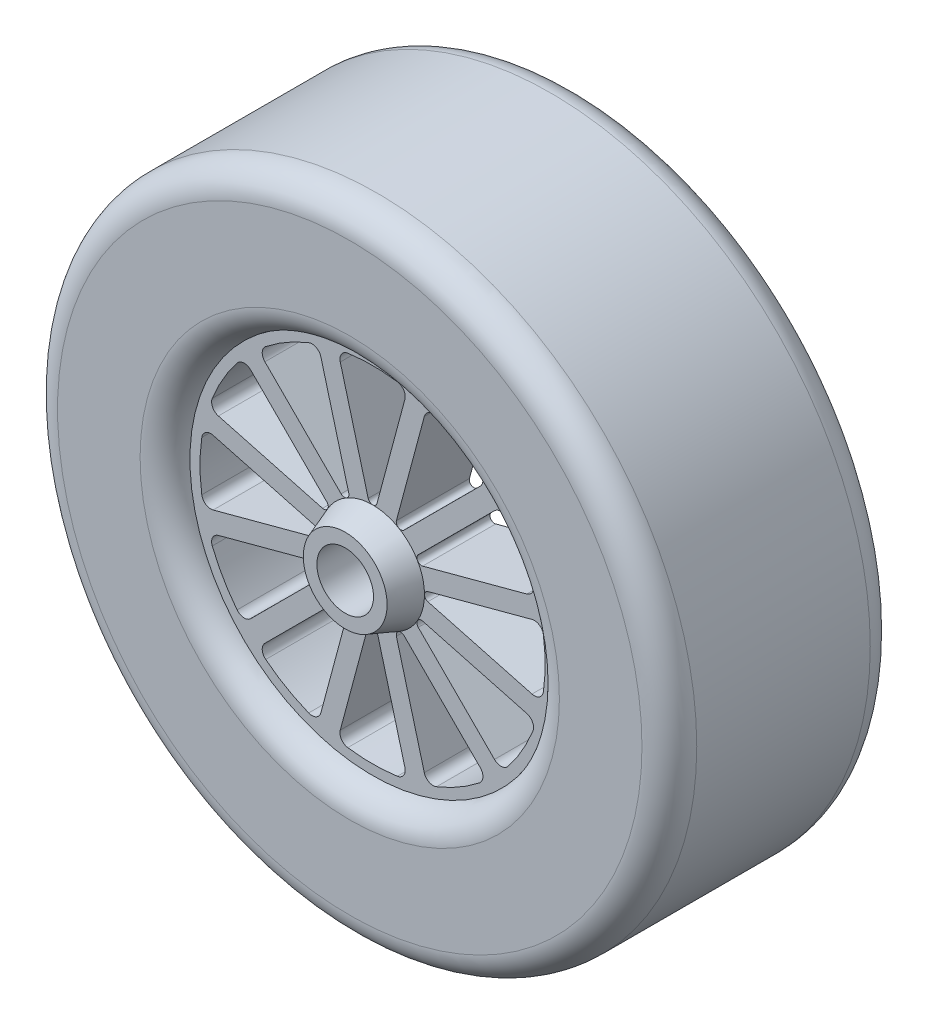
SolidWorks part; units mm, degrees
ref_plane "前视基准面" through (0, 0, 0) normal (0, 0, 1) x (1, 0, 0)
ref_plane "上视基准面" through (0, 0, 0) normal (0, 1, 0) x (1, 0, 0)
ref_plane "右视基准面" through (0, 0, 0) normal (1, 0, 0) x (0, 0, -1)
other "Configuration Table"
sketch "草图1" plane through (0, 0, 0) normal (0, 0, 1) x (1, 0, 0)
  circle A0 centre (0, 0) radius 35
  dimension "D1" = 70
extrude "凸台-拉伸1" add sketch "草图1" along normal mid plane 25
sketch "草图2" plane through (0, 0, 12.5) normal (0, 0, 1) x (1, 0, 0)
  circle A0 centre (0, 0) radius 3.05
  dimension "D1" = 6.1
extrude "切除-拉伸1" cut sketch "草图2" against normal blind 50
sketch "草图3" plane through (0, 0, 12.5) normal (0, 0, 1) x (1, 0, 0)
  circle A0 centre (0, 0) radius 20
  circle A1 centre (0, 0) radius 5
  dimension "D1" = 10
  dimension "D2" = 40
extrude "切除-拉伸2" cut sketch "草图3" against normal blind 2.5
mirror "镜向1" about plane through (0, 0, 0) normal (0, 0, 1) of "切除-拉伸2"
sketch "草图5" plane through (0, 0, -12.5) normal (0, 0, -1) x (-1, 0, 0)
  circle A1 centre (0, 0) radius 5
  circle A5 centre (0, 0) radius 5
  dimension "D1" = 0
extrude "切除-拉伸4" cut sketch "草图5" against normal blind 2.5
mirror "镜向2" about plane through (0, 0, 0) normal (0, 0, 1) of "切除-拉伸4"
fillet "圆角1" radius 3 4 edges at (20, 0, 12.5) (20, 0, -12.5) (35, 0, 12.5) (35, 0, -12.5)
sketch "草图6" plane through (0, 0, 10) normal (0, 0, 1) x (1, 0, 0)
  line L0 (0, 0) -> (0, 36.7469) construction
  line L1 (0, 0) -> (-5.1764, 19.3185)
  line L2 (0, 0) -> (5.1764, 19.3185)
  line L3 (-0.483, 6.0525) -> (-3.5383, 17.4554)
  line L4 (0.483, 6.0525) -> (3.5383, 17.4554)
  line L5 (0, 4.2501) -> (3.8209, 18.5098) construction
  line L6 (0, 4.2501) -> (-3.8209, 18.5098) construction
  line L7 (3.4445, 5.0002) -> (11.792, 13.3476)
  line L8 (2.608, 5.4831) -> (5.6634, 16.886)
  line L9 (5.4831, 2.608) -> (16.886, 5.6634)
  line L10 (5.0002, 3.4445) -> (13.3476, 11.792)
  line L11 (6.0525, -0.483) -> (17.4554, -3.5383)
  line L12 (6.0525, 0.483) -> (17.4554, 3.5383)
  line L13 (5.0002, -3.4445) -> (13.3476, -11.792)
  line L14 (5.4831, -2.608) -> (16.886, -5.6634)
  line L15 (2.608, -5.4831) -> (5.6634, -16.886)
  line L16 (3.4445, -5.0002) -> (11.792, -13.3476)
  line L17 (-0.483, -6.0525) -> (-3.5383, -17.4554)
  line L18 (0.483, -6.0525) -> (3.5383, -17.4554)
  line L19 (-3.4445, -5.0002) -> (-11.792, -13.3476)
  line L20 (-2.608, -5.4831) -> (-5.6634, -16.886)
  line L21 (-5.4831, -2.608) -> (-16.886, -5.6634)
  line L22 (-5.0002, -3.4445) -> (-13.3476, -11.792)
  line L23 (-6.0525, 0.483) -> (-17.4554, 3.5383)
  line L24 (-6.0525, -0.483) -> (-17.4554, -3.5383)
  line L25 (-5.0002, 3.4445) -> (-13.3476, 11.792)
  line L26 (-5.4831, 2.608) -> (-16.886, 5.6634)
  line L27 (-2.608, 5.4831) -> (-5.6634, 16.886)
  line L28 (-3.4445, 5.0002) -> (-11.792, 13.3476)
  arc A0 (3.8209, 18.5098) -> (-3.8209, 18.5098) centre (0, 0) ccw construction
  circle A1 centre (0, 0) radius 20 construction
  arc A2 (5.1764, 19.3185) -> (-5.1764, 19.3185) centre (0, 0) ccw
  arc A4 (2.7161, 18.7038) -> (3.5383, 17.4554) centre (2.5724, 17.7142) cw
  arc A6 (2.7161, 18.7038) -> (-2.7161, 18.7038) centre (0, 0) ccw
  arc A7 (-3.5383, 17.4554) -> (-2.7161, 18.7038) centre (-2.5724, 17.7142) cw
  arc A8 (5.6634, 16.886) -> (6.9997, 17.556) centre (6.6293, 16.6272) cw
  arc A9 (11.7041, 14.8399) -> (6.9997, 17.556) centre (0, 0) ccw
  arc A10 (11.7041, 14.8399) -> (11.792, 13.3476) centre (11.0849, 14.0547) cw
  arc A11 (13.3476, 11.792) -> (14.8399, 11.7041) centre (14.0547, 11.0849) cw
  arc A12 (17.556, 6.9997) -> (14.8399, 11.7041) centre (0, 0) ccw
  arc A13 (17.556, 6.9997) -> (16.886, 5.6634) centre (16.6272, 6.6293) cw
  arc A14 (17.4554, 3.5383) -> (18.7038, 2.7161) centre (17.7142, 2.5724) cw
  arc A15 (18.7038, -2.7161) -> (18.7038, 2.7161) centre (0, 0) ccw
  arc A16 (18.7038, -2.7161) -> (17.4554, -3.5383) centre (17.7142, -2.5724) cw
  arc A17 (16.886, -5.6634) -> (17.556, -6.9997) centre (16.6272, -6.6293) cw
  arc A18 (14.8399, -11.7041) -> (17.556, -6.9997) centre (0, 0) ccw
  arc A19 (14.8399, -11.7041) -> (13.3476, -11.792) centre (14.0547, -11.0849) cw
  arc A20 (11.792, -13.3476) -> (11.7041, -14.8399) centre (11.0849, -14.0547) cw
  arc A21 (6.9997, -17.556) -> (11.7041, -14.8399) centre (0, 0) ccw
  arc A22 (6.9997, -17.556) -> (5.6634, -16.886) centre (6.6293, -16.6272) cw
  arc A23 (3.5383, -17.4554) -> (2.7161, -18.7038) centre (2.5724, -17.7142) cw
  arc A24 (-2.7161, -18.7038) -> (2.7161, -18.7038) centre (0, 0) ccw
  arc A25 (-2.7161, -18.7038) -> (-3.5383, -17.4554) centre (-2.5724, -17.7142) cw
  arc A26 (-5.6634, -16.886) -> (-6.9997, -17.556) centre (-6.6293, -16.6272) cw
  arc A27 (-11.7041, -14.8399) -> (-6.9997, -17.556) centre (0, 0) ccw
  arc A28 (-11.7041, -14.8399) -> (-11.792, -13.3476) centre (-11.0849, -14.0547) cw
  arc A29 (-13.3476, -11.792) -> (-14.8399, -11.7041) centre (-14.0547, -11.0849) cw
  arc A30 (-17.556, -6.9997) -> (-14.8399, -11.7041) centre (0, 0) ccw
  arc A31 (-17.556, -6.9997) -> (-16.886, -5.6634) centre (-16.6272, -6.6293) cw
  arc A32 (-17.4554, -3.5383) -> (-18.7038, -2.7161) centre (-17.7142, -2.5724) cw
  arc A33 (-18.7038, 2.7161) -> (-18.7038, -2.7161) centre (0, 0) ccw
  arc A34 (-18.7038, 2.7161) -> (-17.4554, 3.5383) centre (-17.7142, 2.5724) cw
  arc A35 (-16.886, 5.6634) -> (-17.556, 6.9997) centre (-16.6272, 6.6293) cw
  arc A36 (-14.8399, 11.7041) -> (-17.556, 6.9997) centre (0, 0) ccw
  arc A37 (-14.8399, 11.7041) -> (-13.3476, 11.792) centre (-14.0547, 11.0849) cw
  arc A38 (-11.792, 13.3476) -> (-11.7041, 14.8399) centre (-11.0849, 14.0547) cw
  arc A39 (-6.9997, 17.556) -> (-11.7041, 14.8399) centre (0, 0) ccw
  arc A40 (-6.9997, 17.556) -> (-5.6634, 16.886) centre (-6.6293, 16.6272) cw
  arc A41 (-5.0002, 3.4445) -> (-5.4831, 2.608) centre (-5.3537, 3.091) cw
  arc A42 (3.4445, 5.0002) -> (2.608, 5.4831) centre (3.091, 5.3537) cw
  arc A43 (5.4831, 2.608) -> (5.0002, 3.4445) centre (5.3537, 3.091) cw
  arc A44 (6.0525, -0.483) -> (6.0525, 0.483) centre (6.1819, 0) cw
  arc A45 (5.0002, -3.4445) -> (5.4831, -2.608) centre (5.3537, -3.091) cw
  arc A46 (2.608, -5.4831) -> (3.4445, -5.0002) centre (3.091, -5.3537) cw
  arc A47 (-0.483, -6.0525) -> (0.483, -6.0525) centre (0, -6.1819) cw
  arc A48 (-3.4445, -5.0002) -> (-2.608, -5.4831) centre (-3.091, -5.3537) cw
  arc A49 (-5.4831, -2.608) -> (-5.0002, -3.4445) centre (-5.3537, -3.091) cw
  arc A50 (-6.0525, 0.483) -> (-6.0525, -0.483) centre (-6.1819, 0) cw
  arc A51 (-2.608, 5.4831) -> (-3.4445, 5.0002) centre (-3.091, 5.3537) cw
  arc A52 (-0.483, 6.0525) -> (0.483, 6.0525) centre (0, 6.1819) ccw
  point P96 (0, 0)
  dimension "D3" = 1
  dimension "D5" = 0.5
  dimension "D1" = 30
  dimension "D2" = 1.1
  dimension "D4" = 12
extrude "切除-拉伸5" cut sketch "草图6" against normal through all contours L3 A7 A6 A4 L4 A52 | L27 A40 A39 A38 L28 A51 | L25 A37 A36 A35 L26 A41 | L23 A34 A33 A32 L24 A50 | L21 A31 A30 A29 L22 A49 | L19 A28 A27 A26 L20 A48 | L17 A25 A24 A23 L18 A47 | L15 A22 A21 A20 L16 A46 | L13 A19 A18 A17 L14 A45 | L11 A16 A15 A14 L12 A44 | L9 A13 A12 A11 L10 A43 | L7 A10 A9 A8 L8 A42
sketch "草图7" plane through (0, 0, 0) normal (0, 1, 0) x (1, 0, 0)
  line L0 (0, 0) -> (-42.0641, 0) construction
  line L1 (0, 0) -> (0, 24.0074) construction
  line L3 (-10.2998, -1.6402) -> (-20, 10)
  line L5 (-20, 10) -> (0, 10)
  line L6 (0, 10) -> (0, -2)
  line L7 (0, -2) -> (-9.5316, -2)
  line L12 (20, 10) -> (-20, 10) construction
  arc A0 (-9.5316, -2) -> (-10.2998, -1.6402) centre (-9.5316, -1) cw
  point P20 (-10, -2)
  dimension "D4" = 1
  dimension "D1" = 10
  dimension "D2" = 20
  dimension "D3" = 12
revolve "切除-旋转1" cut sketch "草图7" angle 360 about L1
sketch "草图8" plane through (0, 0, 10) normal (0, 0, 1) x (1, 0, 0)
  circle A0 centre (0, 0) radius 5.6819
  arc A1 (6.0525, 0.483) -> (6.0525, -0.483) centre (6.1819, 0) ccw construction
extrude "凸台-拉伸2" add sketch "草图8" along normal blind 3 draft 20
sketch "草图9" plane through (0, 0, 13) normal (0, 0, 1) x (1, 0, 0)
  circle A0 centre (0, 0) radius 3.1
  dimension "D1" = 6.2
extrude "切除-拉伸6" cut sketch "草图9" against normal through all
